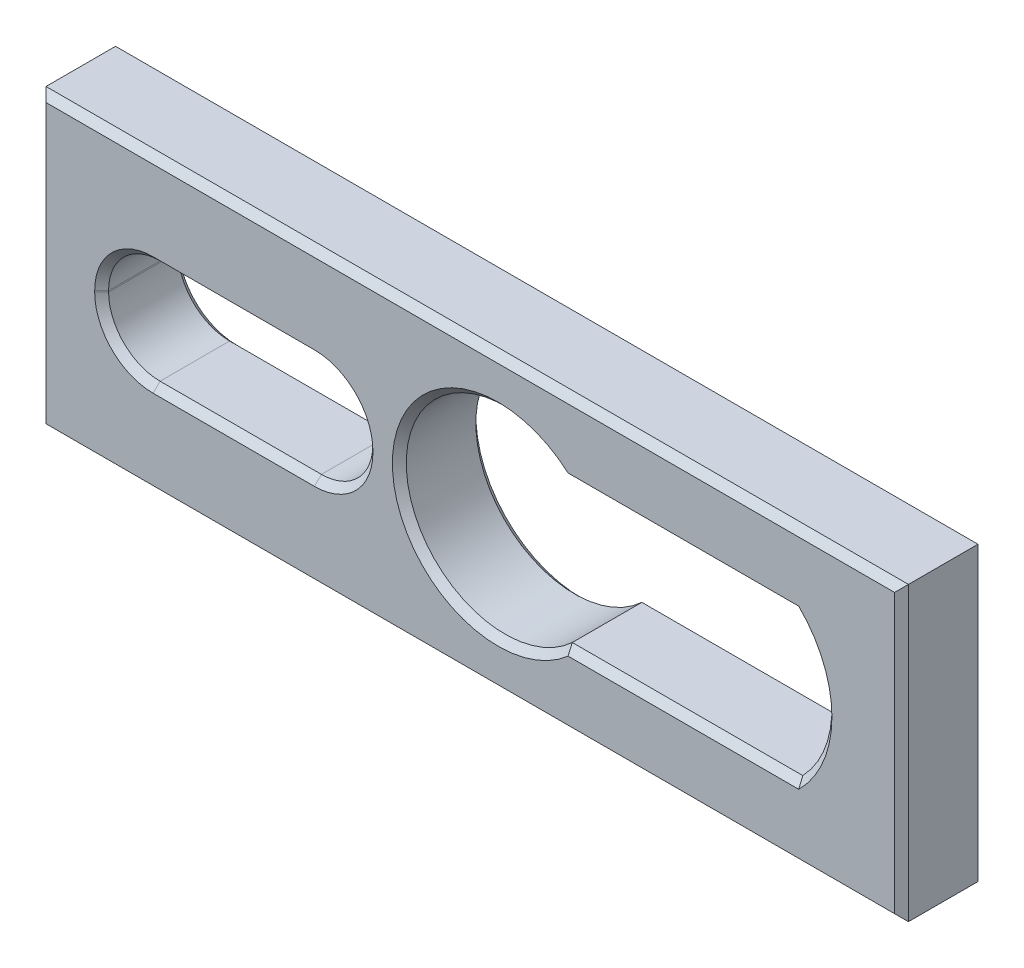
SolidWorks part; units mm, degrees
material "Простая углеродистая сталь"
ref_plane "Спереди" through (0, 0, 0) normal (0, 0, 1) x (1, 0, 0)
ref_plane "Сверху" through (0, 0, 0) normal (0, 1, 0) x (1, 0, 0)
ref_plane "Справа" through (0, 0, 0) normal (1, 0, 0) x (0, 0, -1)
sketch "Эскиз1" plane through (0, 0, 0) normal (0, 0, 1) x (1, 0, 0)
  line L1 (-31, 10.5) -> (31, 10.5)
  line L2 (-31, 10.5) -> (-31, -10.5)
  line L3 (-31, -10.5) -> (31, -10.5)
  line L4 (31, 10.5) -> (31, -10.5)
  line L5 (0, -10.5) -> (0, 10.5) construction
  line L6 (-31, 0) -> (31, 0) construction
  point P0 (0, 0)
  dimension "D1" = 21
  dimension "D2" = 62
extrude "Бобышка-Вытянуть1" add sketch "Эскиз1" along normal blind 6
sketch "Эскиз2" plane through (0, 0, 6) normal (0, 0, 1) x (1, 0, 0)
  line L0 (-31, 0) -> (31, 0) construction
  line L1 (-31, 10.5) -> (-31, -10.5) construction
  line L2 (31, -10.5) -> (31, 10.5) construction
  line L4 (-22.8, 3.75) -> (-11.2, 3.75)
  line L5 (-26.5, 0.05) -> (-26.5, -0.05)
  line L6 (-22.8, -3.75) -> (-11.2, -3.75)
  line L7 (-7.5, 0.05) -> (-7.5, -0.05)
  line L8 (-17, -3.75) -> (-17, 3.75) construction
  line L9 (-26.5, 0) -> (-7.5, 0) construction
  arc A0 (-26.5, -0.05) -> (-22.8, -3.75) centre (-22.8, -0.05) ccw
  arc A1 (-11.2, -3.75) -> (-7.5, -0.05) centre (-11.2, -0.05) ccw
  arc A2 (-11.2, 3.75) -> (-7.5, 0.05) centre (-11.2, 0.05) cw
  arc A3 (-22.8, 3.75) -> (-26.5, 0.05) centre (-22.8, 0.05) ccw
  circle A4 centre (2, 0) radius 7.1
  point P6 (-17, 0)
  point P12 (-26.5, -3.75)
  point P20 (-7.5, 3.75)
  point P23 (-26.5, 3.75)
  dimension "D4" = 3.7
  dimension "D5" = 14.2
  dimension "D1" = 7.5
  dimension "D2" = 19
  dimension "D3" = 4.5
  dimension "D6" = 33
extrude "Вырез-Вытянуть1" cut sketch "Эскиз2" against normal blind 6
sketch "Эскиз3" plane through (0, 0, 6) normal (0, 0, 1) x (1, 0, 0)
  line L0 (0, 0) -> (31, 0) construction
  line L1 (31, -10.5) -> (31, 10.5) construction
  line L2 (23.4046, 5.2) -> (4.5, 5.2)
  line L3 (4.5, 5.2) -> (25.5, 5.2) construction
  line L4 (4.5, 5.2) -> (4.5, -5.2) construction
  line L5 (4.5, -5.2) -> (25.5, -5.2) construction
  line L6 (25.5, 5.2) -> (25.5, -5.2) construction
  line L7 (15, -5.2) -> (15, 5.2) construction
  line L8 (4.5, 0) -> (25.5, 0) construction
  line L9 (4.5, 5.2) -> (4.5, -5.2)
  line L10 (4.5, -5.2) -> (23.4046, -5.2)
  arc A0 (23.4046, 5.2) -> (23.4046, -5.2) centre (18, 0) cw
  point P5 (15, 0)
  dimension "D4" = 7.5
  dimension "D1" = 10.4
  dimension "D2" = 21
  dimension "D3" = 5.5
extrude "Вырез-Вытянуть2" cut sketch "Эскиз3" against normal blind 6
chamfer "Фаска1" distance 0.5 angle 45 32 edges at (0, 10.5, 0) (-31, 0, 0) (0, -10.5, 0) (31, 0, 0) (15.1194, -5.2, 0) (-5.1, 0, 0) (15.1194, 5.2, 0) (25.5, 0, 0) (-25.4163, 2.6663, 0) (-17, 3.75, 0) (-8.5837, 2.6663, 0) (-7.5, 0, 0) (-8.5837, -2.6663, 0) (-17, -3.75, 0) (-25.4163, -2.6663, 0) (-26.5, 0, 0) (0, -10.5, 6) (-31, 0, 6) (0, 10.5, 6) (31, 0, 6) (-17, -3.75, 6) (-8.5837, -2.6663, 6) (-7.5, 0, 6) (-8.5837, 2.6663, 6) (-17, 3.75, 6) (-25.4163, 2.6663, 6) (-26.5, 0, 6) (-25.4163, -2.6663, 6) (-5.1, 0, 6) (15.1194, -5.2, 6) (25.5, 0, 6) (15.1194, 5.2, 6)
